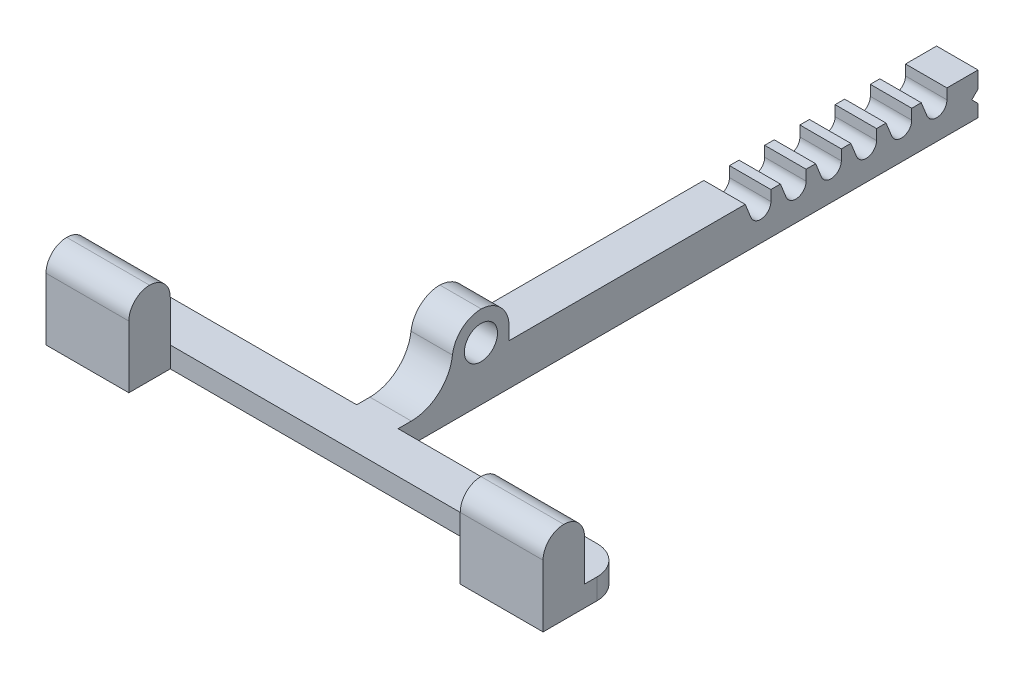
SolidWorks part; units mm, degrees
ref_plane "Front Plane" through (0, 0, 0) normal (0, 0, 1) x (1, 0, 0)
ref_plane "Top Plane" through (0, 0, 0) normal (0, 1, 0) x (1, 0, 0)
ref_plane "Right Plane" through (0, 0, 0) normal (1, 0, 0) x (0, 0, -1)
sketch "Sketch1" plane through (0, 0, 0) normal (0, 1, 0) x (1, 0, 0)
  line L0 (44.6675, -8.5158) -> (60, -8.5158)
  line L1 (0, 0) -> (0, 73.7509) construction
  line L2 (-5, 1.4842) -> (5, 1.4842)
  line L3 (-5, 1.4842) -> (5, 1.4842) construction
  line L4 (-5, 1.4842) -> (-5, 141.4842)
  line L5 (-5, 141.4842) -> (5, 141.4842)
  line L6 (5, 1.4842) -> (5, 141.4842)
  line L7 (-60, -8.5158) -> (44.6675, -8.5158)
  line L8 (-60, -8.5158) -> (-60, 1.4842)
  line L9 (-60, 1.4842) -> (60, 1.4842)
  line L10 (60, -8.5158) -> (60, 1.4842)
  line L11 (-60, -8.5158) -> (60, 1.4842) construction
  line L12 (-60, 1.4842) -> (60, -8.5158) construction
  line L13 (60, -8.5158) -> (40, -8.5158)
  line L14 (60, -8.5158) -> (60, -18.5158)
  line L15 (60, -18.5158) -> (40, -18.5158)
  line L16 (40, -8.5158) -> (40, -18.5158)
  line L17 (-60, -8.5158) -> (-40, -8.5158)
  line L18 (-60, -8.5158) -> (-60, -18.5158)
  line L19 (-60, -18.5158) -> (-40, -18.5158)
  line L20 (-40, -8.5158) -> (-40, -18.5158)
  line L21 (0, -55) -> (0, 55) construction
  line L23 (-5, 28.2887) -> (5, 28.2887)
  line L24 (-5, 28.2887) -> (-5, 14.6797)
  line L25 (-5, 14.6797) -> (5, 14.6797)
  line L26 (5, 28.2887) -> (5, 14.6797)
  line L27 (-5, 28.2887) -> (5, 14.6797) construction
  line L28 (-5, 14.6797) -> (5, 28.2887) construction
  point P0 (0, 0)
  point P5 (0, 21.4842)
  point P6 (0, -3.5158)
  dimension "D1" = 10
  dimension "D2" = 120
  dimension "D3" = 30
  dimension "D4" = 20
  dimension "D5" = 120
extrude "Boss-Extrude1" add sketch "Sketch1" along normal blind 5 contours L7 L16 L15 L14 L0 | L0 L10 L9 L2 L8 L7 | L20 L7 L18 L19 | L25 L4 L2 L6 | L4 L25 L6 L23 | L4 L23 L6 L5 region at (0, 0, 3.5158) region at (50, 0, 13.5158) region at (-50, 0, 13.5158) region at (0, 0, -8.082) region at (0, 0, -21.4842) region at (0, 0, -84.8865)
extrude "Boss-Extrude2" add sketch "Sketch1<3>" along normal blind 20 contours L20 L7 L18 L19 | L7 L16 L15 L14 L0 | L4 L25 L6 L23 region at (50, 0, 13.5158) region at (-50, 0, 13.5158) region at (0, 0, -21.4842)
sketch "Sketch1<3>" plane through (0, 0, 0) normal (0, 1, 0) x (1, 0, 0) same geometry as "Sketch1"
extrude "Boss-Extrude3" add sketch "Sketch1<5>" along normal blind 10 contours L4 L23 L6 L5 region at (0, 0, -84.8865)
sketch "Sketch1<5>" plane through (0, 0, 0) normal (0, 1, 0) x (1, 0, 0) same geometry as "Sketch1"
sketch "Sketch3" plane through (5, 0, 0) normal (1, 0, 0) x (0, 0, -1)
  line L0 (120.6636, 6.5701) -> (119.2891, 10)
  line L1 (28.2887, 10) -> (141.4842, 10) construction
  line L2 (133.9842, 7.5) -> (133.9842, 10)
  line L3 (129.1636, 6.5701) -> (127.7891, 10)
  line L4 (127.7891, 10) -> (133.9842, 10)
  line L5 (141.4842, 6) -> (139.9842, 4.5)
  line L6 (141.4842, 10) -> (141.4842, 0) construction
  line L7 (119.2891, 10) -> (125.4842, 10)
  line L8 (125.4842, 7.5) -> (125.4842, 10)
  line L9 (120.6636, 6.5701) -> (125.4842, 7.5) construction
  line L10 (112.1636, 6.5701) -> (110.7891, 10)
  line L11 (110.7891, 10) -> (116.9842, 10)
  line L12 (116.9842, 7.5) -> (116.9842, 10)
  line L13 (112.1636, 6.5701) -> (116.9842, 7.5) construction
  line L14 (103.6636, 6.5701) -> (102.2891, 10)
  line L15 (102.2891, 10) -> (108.4842, 10)
  line L16 (108.4842, 7.5) -> (108.4842, 10)
  line L17 (103.6636, 6.5701) -> (108.4842, 7.5) construction
  line L18 (95.1636, 6.5701) -> (93.7891, 10)
  line L19 (93.7891, 10) -> (99.9842, 10)
  line L20 (99.9842, 7.5) -> (99.9842, 10)
  line L21 (95.1636, 6.5701) -> (99.9842, 7.5) construction
  line L22 (86.6636, 6.5701) -> (85.2891, 10)
  line L23 (85.2891, 10) -> (91.4842, 10)
  line L24 (91.4842, 7.5) -> (91.4842, 10)
  line L25 (86.6636, 6.5701) -> (91.4842, 7.5) construction
  line L26 (139.9842, 4.5) -> (141.4842, 3)
  line L27 (141.4842, 3) -> (141.4842, 6)
  line L42 (21.4842, 20) -> (21.4842, 5.7881) construction
  line L43 (14.6797, 20) -> (28.2887, 20) construction
  line L44 (28.2887, 13) -> (14.6797, 13) construction
  arc A0 (129.1636, 6.5701) -> (133.9842, 7.5) centre (131.4842, 7.5) ccw
  arc A1 (120.6636, 6.5701) -> (125.4842, 7.5) centre (122.9842, 7.5) ccw
  arc A2 (112.1636, 6.5701) -> (116.9842, 7.5) centre (114.4842, 7.5) ccw
  arc A3 (103.6636, 6.5701) -> (108.4842, 7.5) centre (105.9842, 7.5) ccw
  arc A4 (95.1636, 6.5701) -> (99.9842, 7.5) centre (97.4842, 7.5) ccw
  arc A5 (86.6636, 6.5701) -> (91.4842, 7.5) centre (88.9842, 7.5) ccw
  circle A9 centre (21.4842, 13) radius 4
  dimension "D1" = 10
  dimension "D3" = 2.5
  dimension "D5" = 8
  dimension "D6" = 7
  dimension "D2" = 2.5
  dimension "D7" = 1.5
  dimension "D8" = 4
  dimension "D4" = 6
extrude "Cut-Extrude1" cut sketch "Sketch3" against normal blind 10
fillet "Fillet1" radius 10 1 edges at (0, 5, -14.6797)
fillet "Fillet2" radius 5 4 edges at (-50, 20, 8.5158) (-50, 20, 18.5158) (50, 20, 8.5158) (50, 20, 18.5158)
fillet "Fillet3" radius 7 1 edges at (0, 20, -14.6797)
sketch "Sketch4" plane through (5, 0, 0) normal (1, 0, 0) x (0, 0, -1)
  line L0 (17.4842, 13) -> (14.4777, 13) construction
  line L1 (25.4842, 13) -> (28.2887, 13) construction
  line L2 (28.2887, 20) -> (28.2887, 10) construction
  line L3 (15.981, 13) -> (15.981, 4.1223) construction
  line L4 (26.8865, 13) -> (26.8865, 4.1223) construction
  line L5 (15.981, 7.6336) -> (26.8865, 7.6336) construction
  line L6 (17.4842, 13) -> (17.4842, 7.6336)
  line L7 (25.4842, 13) -> (25.4842, 7.6336)
  line L8 (28.2887, 10) -> (28.2887, 7.6336)
  line L9 (14.4777, 13) -> (14.4777, 7.6336)
  circle A0 centre (21.4842, 13) radius 4 construction
  arc A1 (4.6797, 5) -> (14.6103, 13.8235) centre (4.6797, 15) ccw construction
  circle A2 centre (15.981, 5.8287) radius 2.3489
  circle A3 centre (26.8865, 5.7491) radius 2.3489
  point P23 (6.3755, 10.2076)
fillet "Fillet4" radius 7 1 edges at (0, 20, -28.2887)
fillet "Fillet5" radius 7 2 edges at (-60, 2.5, -1.4842) (60, 2.5, -1.4842)
